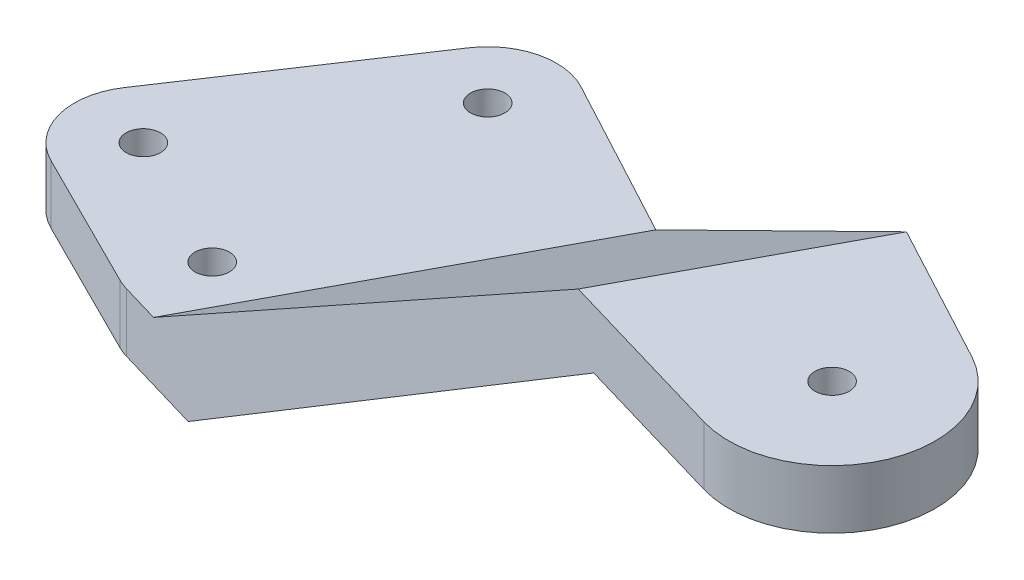
SolidWorks part; units mm, degrees
material "ABS"
ref_plane "Front Plane" through (0, 0, 0) normal (0, 0, 1) x (1, 0, 0)
ref_plane "Top Plane" through (0, 0, 0) normal (0, 1, 0) x (1, 0, 0)
ref_plane "Right Plane" through (0, 0, 0) normal (1, 0, 0) x (0, 0, -1)
sketch "Sketch1" plane through (0, 0, 0) normal (0, 1, 0) x (1, 0, 0)
  line L1 (4.7246, 48.8135) -> (127.0868, -16.7797)
  line L2 (115.7767, -44.3932) -> (-2.8155, -9.5955)
  line L4 (-8.3205, 45.547) -> (-28.3205, 15.547)
  line L5 (-24.4721, 1.0557) -> (-4.4721, -8.9443)
  arc A0 (-8.3205, 45.547) -> (4.7246, 48.8135) centre (0, 40) cw
  arc A1 (127.0868, -16.7797) -> (115.7767, -44.3932) centre (120, -30) cw
  arc A2 (-2.8155, -9.5955) -> (-4.4721, -8.9443) centre (0, 0) cw
  arc A3 (-28.3205, 15.547) -> (-24.4721, 1.0557) centre (-20, 10) ccw
  dimension "D1" = 10
  dimension "D2" = 10
  dimension "D3" = 15
  dimension "D9" = 10
  dimension "D4" = 30
  dimension "D5" = 40
  dimension "D6" = 120
  dimension "D7" = 20
  dimension "D8" = 30
extrude "Boss-Extrude1" add sketch "Sketch1" along normal blind 17
sketch "Sketch2" plane through (0, 17, 0) normal (0, 1, 0) x (1, 0, 0)
  circle A0 centre (0, 40) radius 2.5
  circle A1 centre (0, 0) radius 2.5
  circle A2 centre (120, -30) radius 2.5
  circle A3 centre (-20, 10) radius 2.5
  arc A4 (-28.3205, 15.547) -> (-24.4721, 1.0557) centre (-20, 10) ccw construction
  dimension "D1" = 5
  dimension "D2" = 5
extrude "Cut-Extrude1" cut sketch "Sketch2" against normal through all
sketch "Sketch3" plane through (0, 17, 0) normal (0, 1, 0) x (1, 0, 0)
  line L4 (-2.8155, -9.5955) -> (115.7767, -44.3932)
  line L5 (127.0868, -16.7797) -> (4.7246, 48.8135)
  line L6 (-8.3205, 45.547) -> (-28.3205, 15.547)
  line L7 (-24.4721, 1.0557) -> (-4.4721, -8.9443)
  line L8 (-2.8155, -9.5955) -> (115.7767, -44.3932)
  line L9 (127.0868, -16.7797) -> (4.7246, 48.8135)
  line L10 (-8.3205, 45.547) -> (-28.3205, 15.547)
  line L11 (-24.4721, 1.0557) -> (-4.4721, -8.9443)
  arc A4 (-4.4721, -8.9443) -> (-2.8155, -9.5955) centre (0, 0) ccw
  arc A5 (115.7767, -44.3932) -> (127.0868, -16.7797) centre (120, -30) ccw
  arc A6 (4.7246, 48.8135) -> (-8.3205, 45.547) centre (0, 40) ccw
  arc A7 (-28.3205, 15.547) -> (-24.4721, 1.0557) centre (-20, 10) ccw
  arc A8 (-4.4721, -8.9443) -> (-2.8155, -9.5955) centre (0, 0) ccw
  arc A9 (115.7767, -44.3932) -> (127.0868, -16.7797) centre (120, -30) ccw
  arc A10 (4.7246, 48.8135) -> (-8.3205, 45.547) centre (0, 40) ccw
  arc A11 (-28.3205, 15.547) -> (-24.4721, 1.0557) centre (-20, 10) ccw
  dimension "D1" = 0
extrude "Boss-Extrude2" add sketch "Sketch3" along normal blind 51.5
sketch "Sketch4" plane through (0, 0, 0) normal (0, -1, 0) x (1, 0, 0)
  circle A0 centre (120, 30) radius 2.5 construction
  circle A1 centre (0, -40) radius 2.5 construction
  circle A2 centre (-20, -10) radius 2.5 construction
  circle A3 centre (0, 0) radius 2.5 construction
  circle A4 centre (120, 30) radius 2.5
  circle A5 centre (0, -40) radius 2.5
  circle A6 centre (-20, -10) radius 2.5
  circle A7 centre (0, 0) radius 2.5
extrude "Cut-Extrude2" cut sketch "Sketch4" against normal through all
sketch "Sketch5" plane through (21.3806, 0, -39.8849) normal (0.4725, 0, -0.8814) x (-0.8814, 0, -0.4725)
  line L0 (32.3057, 60) -> (-6.6943, 60)
  line L1 (32.3057, 68.5) -> (32.3057, 0) construction
  line L2 (-6.6943, 60) -> (-96.6943, 0)
  line L3 (-119.9362, 0) -> (18.8983, 0) construction
  line L4 (-96.6943, 0) -> (33.3057, 0)
  line L5 (33.3057, 0) -> (33.3057, 60)
  line L6 (33.3057, 60) -> (32.3057, 60)
  dimension "D1" = 60
  dimension "D2" = 90
  dimension "D3" = 1
  dimension "D4" = 130
extrude "Cut-Extrude3" [suppressed] cut sketch "Sketch5" against normal through all
sketch "Sketch6" plane through (21.3806, 0, -39.8849) normal (0.4725, 0, -0.8814) x (-0.8814, 0, -0.4725)
  line L0 (-134.9362, 8.5) -> (-99.9362, 8.5)
  line L1 (-134.9362, 68.5) -> (-134.9362, 0) construction
  line L2 (-99.9362, 8.5) -> (-14.9362, 68.5)
  line L3 (-119.9362, 68.5) -> (18.8983, 68.5) construction
  line L4 (-14.9362, 68.5) -> (-135.9362, 68.5)
  line L5 (-135.9362, 68.5) -> (-135.9362, 8.5)
  line L6 (-135.9362, 8.5) -> (-134.9362, 8.5)
  dimension "D1" = 121
  dimension "D2" = 1
  dimension "D3" = 35
  dimension "D4" = 60
extrude "Cut-Extrude4" [suppressed] cut sketch "Sketch6" against normal through all
sketch "Sketch7" plane through (21.3806, 0, -39.8849) normal (0.4725, 0, -0.8814) x (-0.8814, 0, -0.4725)
  line L0 (32.3057, 8.5) -> (-7.6943, 8.5)
  line L1 (32.3057, 68.5) -> (32.3057, 0) construction
  line L2 (-7.6943, 8.5) -> (-96.6943, 68.5)
  line L3 (-119.9362, 68.5) -> (18.8983, 68.5) construction
  line L4 (-96.6943, 68.5) -> (33.3057, 68.5)
  line L5 (33.3057, 68.5) -> (33.3057, 8.5)
  line L6 (33.3057, 8.5) -> (32.3057, 8.5)
  dimension "D1" = 1
  dimension "D2" = 130
  dimension "D3" = 60
  dimension "D4" = 40
extrude "Cut-Extrude5" cut sketch "Sketch7" against normal through all
sketch "Sketch8" plane through (21.3806, 0, -39.8849) normal (0.4725, 0, -0.8814) x (-0.8814, 0, -0.4725)
  line L0 (-14.9362, 0) -> (-99.9362, 60)
  line L1 (-119.9362, 0) -> (18.8983, 0) construction
  line L2 (-99.9362, 60) -> (-134.9362, 60)
  line L3 (-134.9362, 68.5) -> (-134.9362, 0) construction
  line L4 (-134.9362, 60) -> (-135.9362, 60)
  line L5 (-135.9362, 60) -> (-135.9362, 0)
  line L6 (-135.9362, 0) -> (-14.9362, 0)
  dimension "D1" = 121
  dimension "D2" = 1
  dimension "D3" = 35
  dimension "D4" = 60
extrude "Cut-Extrude6" cut sketch "Sketch8" against normal through all
